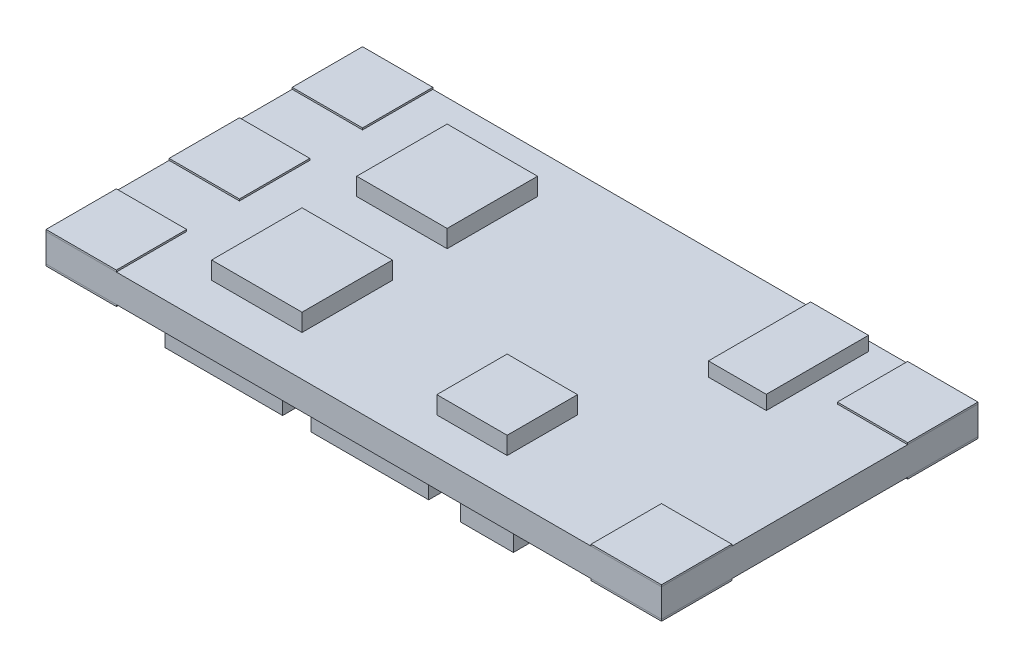
SolidWorks part; units mm, degrees
ref_plane "Front Plane" through (0, 0, 0) normal (0, 0, 1) x (1, 0, 0)
ref_plane "Top Plane" through (0, 0, 0) normal (0, 1, 0) x (1, 0, 0)
ref_plane "Right Plane" through (0, 0, 0) normal (1, 0, 0) x (0, 0, -1)
sketch "Sketch1" plane through (0, 0, 0) normal (0, 1, 0) x (1, 0, 0)
  line L1 (-17.5, -9) -> (17.5, -9)
  line L2 (-17.5, -9) -> (-17.5, 9)
  line L3 (-17.5, 9) -> (17.5, 9)
  line L4 (17.5, -9) -> (17.5, 9)
  line L5 (0, 9) -> (0, -9) construction
  line L6 (-17.5, 0) -> (17.5, 0) construction
  point P0 (0, 0)
  dimension "D1" = 35
  dimension "D2" = 18
extrude "Boss-Extrude1" add sketch "Sketch1" along normal blind 1.6
sketch "Sketch2" plane through (0, 1.6, 0) normal (0, 1, 0) x (1, 0, 0)
  line L1 (8.5094, 2.6608) -> (11.8, 2.6608)
  line L2 (8.5094, 2.6608) -> (8.5094, 8.4708)
  line L3 (8.5094, 8.4708) -> (11.8, 8.4708)
  line L4 (11.8, 2.6608) -> (11.8, 8.4708)
  line L5 (10.1547, 8.4708) -> (10.1547, 2.6608) construction
  line L6 (8.5094, 5.5658) -> (11.8, 5.5658) construction
  point P0 (10.1547, 5.5658)
extrude "Boss-Extrude2" add sketch "Sketch2" along normal blind 0.8 separate body
sketch "Sketch3" plane through (0, 1.6, 0) normal (0, 1, 0) x (1, 0, 0)
  line L1 (2.6479, -6.9231) -> (6.6479, -6.9231)
  line L2 (2.6479, -6.9231) -> (2.6479, -2.9231)
  line L3 (2.6479, -2.9231) -> (6.6479, -2.9231)
  line L4 (6.6479, -6.9231) -> (6.6479, -2.9231)
  line L5 (4.6479, -2.9231) -> (4.6479, -6.9231) construction
  line L6 (2.6479, -4.9231) -> (6.6479, -4.9231) construction
  point P0 (4.6479, -4.9231)
  dimension "D1" = 4
extrude "Boss-Extrude3" add sketch "Sketch3" along normal blind 1 separate body
sketch "Sketch4" plane through (0, 1.6, 0) normal (0, 1, 0) x (1, 0, 0)
  line L0 (-17.5, 0) -> (17.5, 0) construction
  line L5 (-17.5, 9) -> (-17.5, -9) construction
  line L6 (17.5, -9) -> (17.5, 9) construction
  line L7 (-10.3861, -6.697) -> (-5.2444, -6.697)
  line L8 (-10.3861, -6.697) -> (-10.3861, -1.5553)
  line L9 (-10.3861, -1.5553) -> (-5.2444, -1.5553)
  line L10 (-5.2444, -6.697) -> (-5.2444, -1.5553)
  line L11 (-7.8153, -1.5553) -> (-7.8153, -6.697) construction
  line L12 (-10.3861, -4.1261) -> (-5.2444, -4.1261) construction
  line L13 (-10.3861, 1.5553) -> (-5.2444, 1.5553)
  line L14 (-5.2444, 6.697) -> (-5.2444, 1.5553)
  line L15 (-10.3861, 6.697) -> (-5.2444, 6.697)
  line L16 (-10.3861, 6.697) -> (-10.3861, 1.5553)
  point P4 (-7.8153, -4.1261)
extrude "Boss-Extrude4" add sketch "Sketch4" along normal blind 1 separate body
sketch "Sketch5" plane through (0, 1.6, 0) normal (0, 1, 0) x (1, 0, 0)
  line L0 (-17.5, 9) -> (-17.5, -9) construction
  line L1 (-13.5, 5) -> (-17.5, 5)
  line L2 (-13.5, 5) -> (-13.5, 9)
  line L3 (-13.5, 9) -> (-17.5, 9)
  line L4 (-17.5, 5) -> (-17.5, 9)
  line L5 (-15.5, 9) -> (-15.5, 5) construction
  line L6 (-13.5, 7) -> (-17.5, 7) construction
  line L7 (-13.5, -2) -> (-17.5, -2)
  line L8 (-13.5, -2) -> (-13.5, 2)
  line L9 (-13.5, 2) -> (-17.5, 2)
  line L10 (-17.5, -2) -> (-17.5, 2)
  line L11 (-15.5, 2) -> (-15.5, -2) construction
  line L12 (-13.5, 0) -> (-17.5, 0) construction
  line L13 (13.5, -9) -> (17.5, -9)
  line L14 (-13.5, -5) -> (-17.5, -5)
  line L15 (-13.5, -5) -> (-13.5, -9)
  line L16 (-13.5, -9) -> (-17.5, -9)
  line L17 (-17.5, -5) -> (-17.5, -9)
  line L18 (-15.5, -9) -> (-15.5, -5) construction
  line L19 (-13.5, -7) -> (-17.5, -7) construction
  line L20 (13.5, 5) -> (17.5, 5)
  line L21 (13.5, 5) -> (13.5, 9)
  line L22 (13.5, 9) -> (17.5, 9)
  line L23 (17.5, 5) -> (17.5, 9)
  line L24 (15.5, 9) -> (15.5, 5) construction
  line L25 (13.5, 7) -> (17.5, 7) construction
  line L26 (17.5, -5) -> (17.5, -9)
  line L27 (13.5, -5) -> (17.5, -5)
  line L28 (13.5, -5) -> (13.5, -9)
  point P0 (-15.5, 7)
  point P4 (-15.5, 0)
  point P10 (-15.5, -7)
  point P14 (15.5, 7)
  point P18 (0, 0)
  dimension "D1" = 4
extrude "Boss-Extrude5" add sketch "Sketch5" along normal blind 0.1 separate body
ref_plane "Plane1" through (0, 0.8, 0) normal (0, 1, 0) x (1, 0, 0)
mirror "Mirror1" about plane through (0, 0.8, 0) normal (0, 1, 0) of bodies 106 107 108 109 110
sketch "Sketch6" plane through (0, 0, 0) normal (0, -1, 0) x (1, 0, 0)
  line L0 (-4, 9) -> (-4, -9) construction
  line L1 (-17.5, 9) -> (17.5, 9) construction
  line L2 (17.5, -9) -> (-17.5, -9) construction
  line L3 (-17.5, -9) -> (-17.5, 9) construction
  line L4 (-11.5, -8.238) -> (-4.8052, -8.238)
  line L5 (-11.5, 3.762) -> (-4.8052, 3.762)
  line L6 (-11.5, 3.762) -> (-11.5, 8.238)
  line L7 (-11.5, 8.238) -> (-4.8052, 8.238)
  line L8 (-4.8052, 3.762) -> (-4.8052, 8.238)
  line L9 (-8.1526, 8.238) -> (-8.1526, 3.762) construction
  line L10 (-11.5, 6) -> (-4.8052, 6) construction
  line L11 (-11.5, -2.238) -> (-4.8052, -2.238)
  line L12 (-11.5, -2.238) -> (-11.5, 2.238)
  line L13 (-11.5, 2.238) -> (-4.8052, 2.238)
  line L14 (-4.8052, -2.238) -> (-4.8052, 2.238)
  line L15 (-8.1526, 2.238) -> (-8.1526, -2.238) construction
  line L16 (-11.5, 0) -> (-4.8052, 0) construction
  line L17 (-4.8052, -3.762) -> (-4.8052, -8.238)
  line L18 (-11.5, -3.762) -> (-4.8052, -3.762)
  line L19 (-11.5, -3.762) -> (-11.5, -8.238)
  line L20 (3.5, -3.762) -> (3.5, -8.238)
  line L21 (3.5, -3.762) -> (-3.1948, -3.762)
  line L22 (-3.1948, -3.762) -> (-3.1948, -8.238)
  line L23 (3.5, -8.238) -> (-3.1948, -8.238)
  line L24 (3.5, 2.238) -> (-3.1948, 2.238)
  line L25 (-3.1948, -2.238) -> (-3.1948, 2.238)
  line L26 (3.5, -2.238) -> (-3.1948, -2.238)
  line L27 (3.5, -2.238) -> (3.5, 2.238)
  line L28 (3.5, 8.238) -> (-3.1948, 8.238)
  line L29 (-3.1948, 3.762) -> (-3.1948, 8.238)
  line L30 (3.5, 3.762) -> (-3.1948, 3.762)
  line L31 (3.5, 3.762) -> (3.5, 8.238)
  point P8 (-8.1526, 6)
  point P12 (-8.1526, 0)
  point P16 (-4.8052, 3.762)
  dimension "D1" = 13.5
  dimension "D2" = 6
  dimension "D3" = 6
extrude "Boss-Extrude6" add sketch "Sketch6" along normal blind 1.5 separate body
sketch "Sketch7" plane through (0, 0, 0) normal (0, -1, 0) x (1, 0, 0)
  line L0 (7, 9) -> (7, -9) construction
  line L1 (-17.5, 9) -> (17.5, 9) construction
  line L2 (17.5, -9) -> (-17.5, -9) construction
  line L3 (17.5, 9) -> (17.5, -9) construction
  line L4 (5.5, 4.6444) -> (5.5, 6.2444)
  line L5 (5.5, 6.8222) -> (8.5, 6.8222)
  line L6 (5.5, 6.8222) -> (5.5, 8.4222)
  line L7 (5.5, 8.4222) -> (8.5, 8.4222)
  line L8 (8.5, 6.8222) -> (8.5, 8.4222)
  line L9 (7, 8.4222) -> (7, 6.8222) construction
  line L10 (5.5, 7.6222) -> (8.5, 7.6222) construction
  line L11 (5.5, 4.6444) -> (8.5, 4.6444)
  line L12 (8.5, 4.6444) -> (8.5, 6.2444)
  line L13 (5.5, 6.2444) -> (8.5, 6.2444)
  line L14 (5.5, 2.4667) -> (5.5, 4.0667)
  line L15 (5.5, 2.4667) -> (8.5, 2.4667)
  line L16 (8.5, 2.4667) -> (8.5, 4.0667)
  line L17 (5.5, 4.0667) -> (8.5, 4.0667)
  line L18 (5.5, 0.2889) -> (5.5, 1.8889)
  line L19 (5.5, 0.2889) -> (8.5, 0.2889)
  line L20 (8.5, 0.2889) -> (8.5, 1.8889)
  line L21 (5.5, 1.8889) -> (8.5, 1.8889)
  line L22 (5.5, -1.8889) -> (5.5, -0.2889)
  line L23 (5.5, -1.8889) -> (8.5, -1.8889)
  line L24 (8.5, -1.8889) -> (8.5, -0.2889)
  line L25 (5.5, -0.2889) -> (8.5, -0.2889)
  line L26 (5.5, -4.0667) -> (5.5, -2.4667)
  line L27 (5.5, -4.0667) -> (8.5, -4.0667)
  line L28 (8.5, -4.0667) -> (8.5, -2.4667)
  line L29 (5.5, -2.4667) -> (8.5, -2.4667)
  line L30 (5.5, -6.2444) -> (5.5, -4.6444)
  line L31 (5.5, -6.2444) -> (8.5, -6.2444)
  line L32 (8.5, -6.2444) -> (8.5, -4.6444)
  line L33 (5.5, -4.6444) -> (8.5, -4.6444)
  line L34 (5.5, -8.4222) -> (5.5, -6.8222)
  line L35 (5.5, -8.4222) -> (8.5, -8.4222)
  line L36 (8.5, -8.4222) -> (8.5, -6.8222)
  line L37 (5.5, -6.8222) -> (8.5, -6.8222)
  line L38 (8.5, -8.4222) -> (8.5, -9) construction
  line L39 (8.5, 8.4222) -> (8.5, 9) construction
  line L40 (8.5, 6.8222) -> (8.5, 6.2444) construction
  point P8 (7, 7.6222)
  dimension "D1" = 10.5
  dimension "D3" = 1.6
  dimension "D4" = 3
  dimension "D2" = 8
extrude "Boss-Extrude7" add sketch "Sketch7" along normal blind 1.5 separate body
